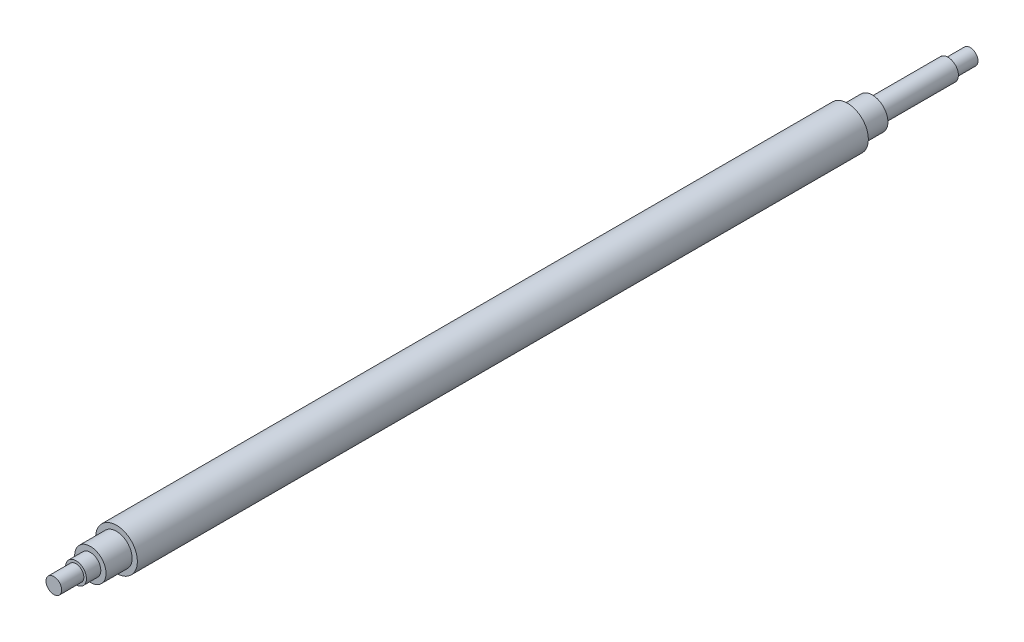
SolidWorks part; units mm, degrees
ref_plane "Piano frontale" through (0, 0, 0) normal (0, 0, 1) x (1, 0, 0)
ref_plane "Piano superiore" through (0, 0, 0) normal (0, 1, 0) x (1, 0, 0)
ref_plane "Piano destro" through (0, 0, 0) normal (1, 0, 0) x (0, 0, -1)
sketch "Schizzo2" plane through (0, 0, 0) normal (1, 0, 0) x (0, 0, -1)
  line L0 (0, 0) -> (0, 3)
  line L1 (0, 3) -> (8.5, 3)
  line L2 (8.5, 3) -> (8.5, 4)
  line L3 (8.5, 4) -> (14, 4)
  line L4 (14, 4) -> (14, 6)
  line L5 (14, 6) -> (24, 6)
  line L6 (24, 6) -> (24, 8)
  line L7 (24, 8) -> (304, 8)
  line L8 (304, 8) -> (304, 6)
  line L9 (304, 6) -> (313.5, 6)
  line L10 (313.5, 6) -> (313.5, 4)
  line L11 (351, 0) -> (0, 0)
  line L14 (351, 0) -> (351, 3)
  line L15 (0, 0) -> (351.0218, 0) construction
  line L16 (342.5, 3) -> (351, 3)
  line L17 (342.5, 4) -> (342.5, 3)
  line L18 (313.5, 4) -> (342.5, 4)
  point P33 (0, 0)
  dimension "D2" = 6
  dimension "D3" = 8
  dimension "D4" = 12
  dimension "D5" = 16
  dimension "D6" = 12
  dimension "D7" = 8
  dimension "D8" = 8.5
  dimension "D9" = 5.5
  dimension "D10" = 10
  dimension "D11" = 280
  dimension "D12" = 9.5
  dimension "D13" = 29
  dimension "D14" = 8.5
  dimension "D15" = 6
revolve "Rivoluzione2" add sketch "Schizzo2" angle 360 about L15
